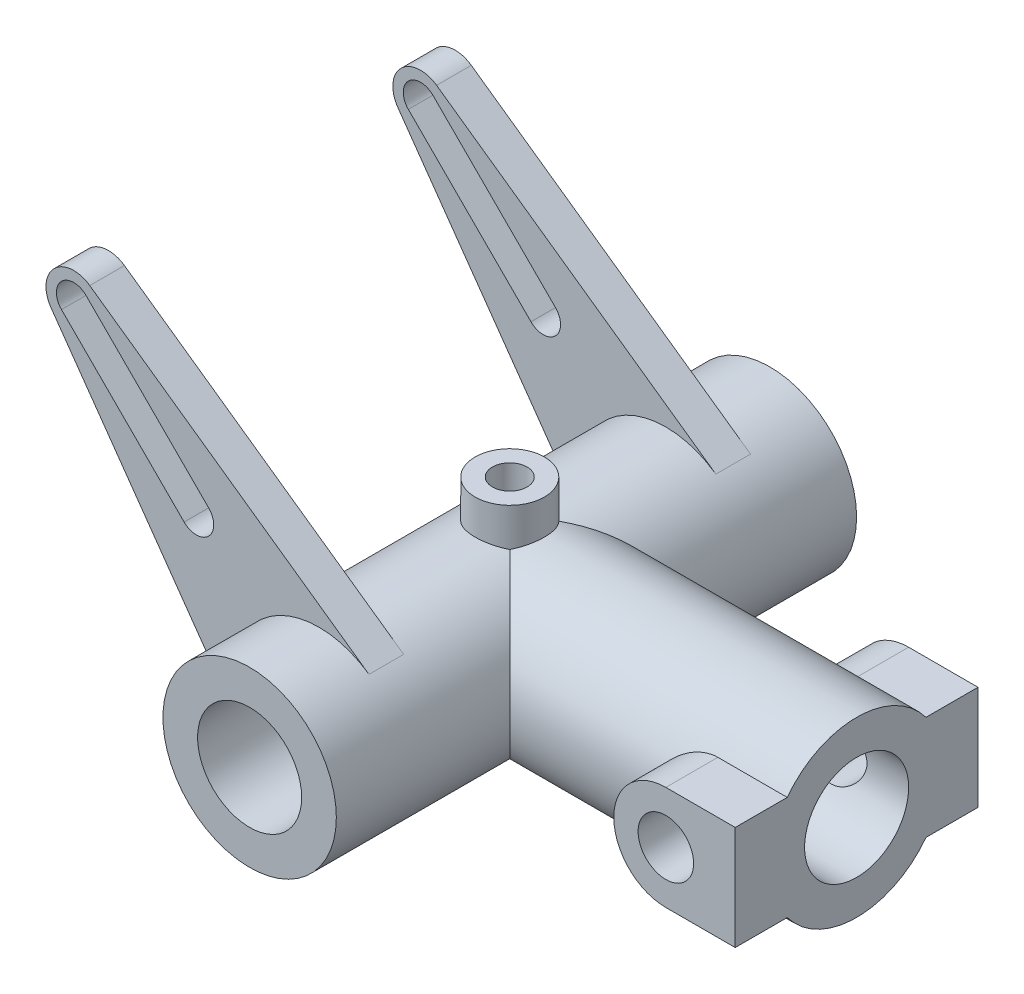
SolidWorks part; units mm, degrees
ref_plane "Alzado" through (0, 0, 0) normal (0, 0, 1) x (1, 0, 0)
ref_plane "Planta" through (0, 0, 0) normal (0, 1, 0) x (1, 0, 0)
ref_plane "Vista lateral" through (0, 0, 0) normal (1, 0, 0) x (0, 0, -1)
sketch "Croquis1" plane through (0, 0, 0) normal (0, 0, 1) x (1, 0, 0)
  circle A0 centre (0, 0) radius 15
  circle A1 centre (0, 0) radius 25
  dimension "D1" = 30
  dimension "D2" = 50
extrude "Saliente-Extruir1" add sketch "Croquis1" along normal mid plane 150
sketch "Croquis2" plane through (0, 0, 0) normal (1, 0, 0) x (0, 0, -1)
  circle A0 centre (0, 0) radius 25
  circle A1 centre (0, 0) radius 15
  dimension "D1" = 50
  dimension "D2" = 30
extrude "Saliente-Extruir3" add sketch "Croquis2" against normal up to surface (75 mm away) from offset 100 up to face at (25, 0, 75)
extrude "Cortar-Extruir1" cut sketch "Croquis2<2>" along normal up to next contours A1
sketch "Croquis2<2>" plane through (0, 0, 0) normal (1, 0, 0) x (0, 0, -1) same geometry as "Croquis2"
sketch "Croquis3" plane through (0, 0, 0) normal (0, 0, 1) x (1, 0, 0)
  line L0 (100, -25) -> (100, 25) construction
  line L1 (100, 15) -> (65, 15)
  line L2 (100, 15) -> (100, -15)
  line L3 (100, -15) -> (65, -15)
  line L4 (65, 15) -> (65, -15)
  point P6 (65, 0)
  dimension "D1" = 30
  dimension "D2" = 35
extrude "Saliente-Extruir4" add sketch "Croquis3" against normal up to surface (15 mm away) from offset 35 up to face at (100, 0, -25)
fillet "Redondeo1" radius 15 2 edges at (65, 15, 27.5) (65, -15, 27.5)
sketch "Croquis4" plane through (0, 0, 35) normal (0, 0, 1) x (1, 0, 0)
  circle A0 centre (80, 0) radius 8
  dimension "D1" = 16
extrude "Cortar-Extruir2" cut sketch "Croquis4" against normal through all
sketch "Croquis5" plane through (0, 0, 0) normal (0, 0, 1) x (1, 0, 0)
  line L0 (14.4152, 20.4256) -> (-66.0978, 77.2469)
  line L1 (-77.2469, 66.0978) -> (-20.4256, -14.4152)
  line L2 (-70.7107, 70.7107) -> (-35.3553, 35.3553) construction
  line L3 (-67.1751, 74.2462) -> (-31.8198, 38.8909)
  line L4 (-74.2462, 67.1751) -> (-38.8909, 31.8198)
  line L5 (0, 0) -> (-35.3553, 35.3553) construction
  arc A0 (-66.0978, 77.2469) -> (-77.2469, 66.0978) centre (-70.7107, 70.7107) ccw
  circle A1 centre (0, 0) radius 25
  circle A2 centre (0, 0) radius 25
  arc A3 (-67.1751, 74.2462) -> (-74.2462, 67.1751) centre (-70.7107, 70.7107) ccw
  arc A4 (-38.8909, 31.8198) -> (-31.8198, 38.8909) centre (-35.3553, 35.3553) ccw
  point P7 (-53.033, 53.033)
  dimension "D2" = 8
  dimension "D3" = 5
  dimension "D4" = 50
  dimension "D5" = 50
  dimension "D6" = 45
  dimension "D1" = 0
extrude "Saliente-Extruir5" add sketch "Croquis5" along normal blind 10 from offset 45 contours A2 L0 A0 L1 A4 L4 A3 L3 region at (-18.6089, 18.6089, 0)
sketch "Croquis6" plane through (0, 0, 0) normal (0, 1, 0) x (1, 0, 0)
  circle A0 centre (0, 0) radius 10
  circle A1 centre (0, 0) radius 5
  dimension "D1" = 20
  dimension "D2" = 10
extrude "Saliente-Extruir6" add sketch "Croquis6" against normal up to surface (10 mm away) from offset 35 up to face at (-10.3414, 10.3414, 50)
extrude "Cortar-Extruir3" cut sketch "Croquis6<2>" along normal up to next contours A1
sketch "Croquis6<2>" plane through (0, 0, 0) normal (0, 1, 0) x (1, 0, 0) same geometry as "Croquis6"
mirror "Simetría1" about plane through (0, 0, 0) normal (0, 0, 1) of "Saliente-Extruir5", "Cortar-Extruir2", "Redondeo1", "Saliente-Extruir4"
